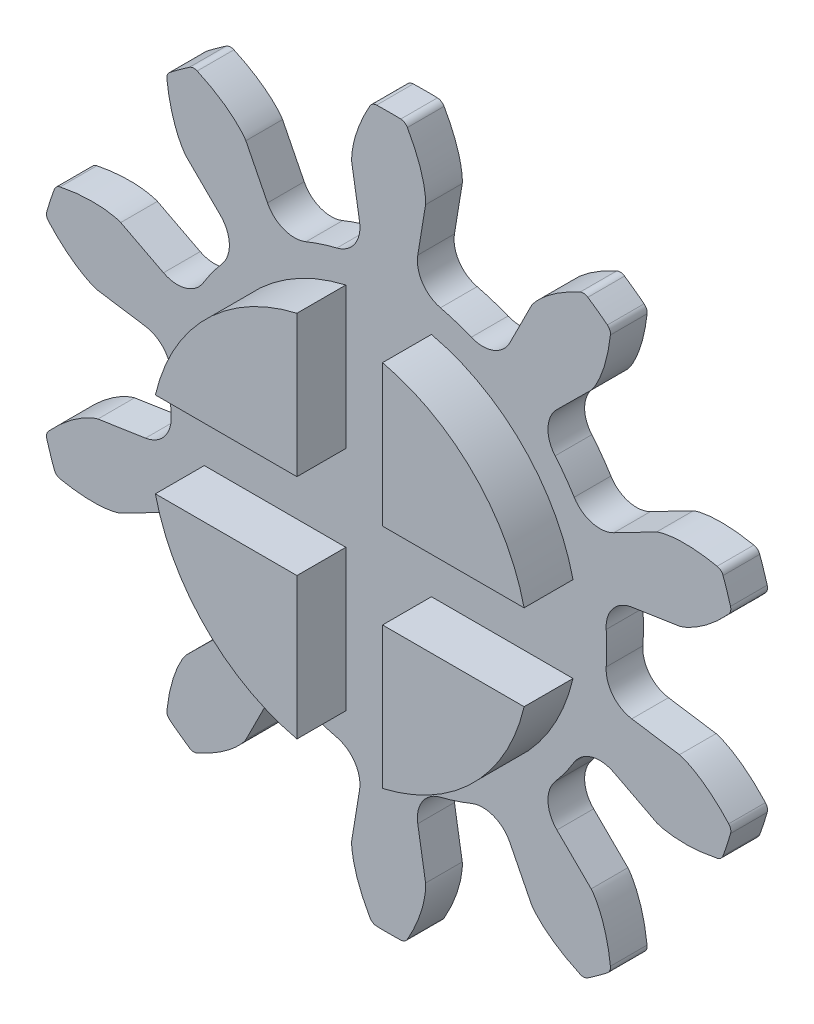
SolidWorks part; units mm, degrees
ref_plane "Front Plane" through (0, 0, 0) normal (0, 0, 1) x (1, 0, 0)
ref_plane "Top Plane" through (0, 0, 0) normal (0, 1, 0) x (1, 0, 0)
ref_plane "Right Plane" through (0, 0, 0) normal (1, 0, 0) x (0, 0, -1)
sketch "Sketch1" plane through (0, 0, 0) normal (0, 0, 1) x (1, 0, 0)
  circle A0 centre (0, 0) radius 38.1
  dimension "D1" = 76.2
extrude "Boss-Extrude1" add sketch "Sketch1" along normal blind 3.81
sketch "Sketch2" plane through (0, 0, 0) normal (0, 0, 1) x (1, 0, 0)
  line L0 (30.3864, 4.6402) -> (0, 0) construction
  line L1 (0, 0) -> (30.3864, -4.6402) construction
  line L2 (30.3864, -4.6402) -> (23.5396, -3.5946)
  line L3 (30.3864, 4.6402) -> (23.5396, 3.5946)
  line L4 (0, 0) -> (31.3591, -4.9668) construction
  circle A0 centre (0, 0) radius 38.1 construction
  circle A1 centre (0, 0) radius 23.8125 construction
  circle A2 centre (0, 0) radius 30.7387 construction
  circle A3 centre (0, 0) radius 31.75 construction
  arc A4 (36.8988, 9.4914) -> (36.8988, -9.4914) centre (48.4711, 0) cw
  arc A5 (23.5396, 3.5946) -> (23.5396, -3.5946) centre (0, 0) cw
  spline S0 degree 4 poles (30.3864, 4.6402) (30.3985, 4.6422) (30.4321, 4.6485) (30.4952, 4.6626) (30.5976, 4.6888) (30.7269, 4.7269) (30.8928, 4.7816) (31.0863, 4.8528) (31.2968, 4.9382) (31.5235, 5.0388) (31.7473, 5.1459) (31.9683, 5.2589) (32.1864, 5.377) (32.448, 5.5266) (32.7579, 5.715) (33.1145, 5.9482) (33.5119, 6.2279) (33.9091, 6.5289) (34.2933, 6.8381) (34.6734, 7.1653) (35.0354, 7.4922) (35.4028, 7.8465) (35.7374, 8.181) (36.1023, 8.5717) (36.3938, 8.8916) (36.7672, 9.3302) (36.9844, 9.5942) (37.2346, 9.9087) (37.3436, 10.0513) (37.4108, 10.139) knots 0 0 0 0 0 0.005377 0.015084 0.028532 0.04661 0.064855 0.092111 0.119476 0.146842 0.174209 0.201575 0.228941 0.256307 0.307035 0.361767 0.4165 0.471232 0.525964 0.580697 0.635429 0.690161 0.744894 0.799626 0.854358 0.909091 0.954545 1 1 1 1 1 construction
  spline S1 degree 4 poles (30.3864, 4.6402) (30.3985, 4.6422) (30.4321, 4.6485) (30.4952, 4.6626) (30.5976, 4.6888) (30.7269, 4.7269) (30.8928, 4.7816) (31.0863, 4.8528) (31.2968, 4.9382) (31.5235, 5.0388) (31.7473, 5.1459) (31.9683, 5.2589) (32.1864, 5.377) (32.448, 5.5266) (32.7579, 5.715) (33.1145, 5.9482) (33.5119, 6.2279) (33.9091, 6.5289) (34.2933, 6.8381) (34.6734, 7.1653) (35.0354, 7.4922) (35.4028, 7.8465) (35.7374, 8.181) (36.1023, 8.5717) (36.3938, 8.8916) (36.6863, 9.2351) (36.8273, 9.4042) (36.8988, 9.4914) knots 0 0 0 0 0 0.005377 0.015084 0.028532 0.04661 0.064855 0.092111 0.119476 0.146842 0.174209 0.201575 0.228941 0.256307 0.307035 0.361767 0.4165 0.471232 0.525964 0.580697 0.635429 0.690161 0.744894 0.799626 0.854358 0.909091 0.909091 0.909091 0.909091 0.909091
  spline S2 degree 4 poles (30.3864, -4.6402) (30.3985, -4.6422) (30.4321, -4.6485) (30.4952, -4.6626) (30.5976, -4.6888) (30.7269, -4.7269) (30.8928, -4.7816) (31.0863, -4.8528) (31.2968, -4.9382) (31.5235, -5.0388) (31.7473, -5.1459) (31.9683, -5.2589) (32.1864, -5.377) (32.448, -5.5266) (32.7579, -5.715) (33.1145, -5.9482) (33.5119, -6.2279) (33.9091, -6.5289) (34.2933, -6.8381) (34.6734, -7.1653) (35.0354, -7.4922) (35.4028, -7.8465) (35.7374, -8.181) (36.1023, -8.5717) (36.3938, -8.8916) (36.7672, -9.3302) (36.9844, -9.5942) (37.2346, -9.9087) (37.3436, -10.0513) (37.4108, -10.139) knots 0 0 0 0 0 0.005377 0.015084 0.028532 0.04661 0.064855 0.092111 0.119476 0.146842 0.174209 0.201575 0.228941 0.256307 0.307035 0.361767 0.4165 0.471232 0.525964 0.580697 0.635429 0.690161 0.744894 0.799626 0.854358 0.909091 0.954545 1 1 1 1 1 construction
  spline S3 degree 4 poles (30.3864, -4.6402) (30.3985, -4.6422) (30.4321, -4.6485) (30.4952, -4.6626) (30.5976, -4.6888) (30.7269, -4.7269) (30.8928, -4.7816) (31.0863, -4.8528) (31.2968, -4.9382) (31.5235, -5.0388) (31.7473, -5.1459) (31.9683, -5.2589) (32.1864, -5.377) (32.448, -5.5266) (32.7579, -5.715) (33.1145, -5.9482) (33.5119, -6.2279) (33.9091, -6.5289) (34.2933, -6.8381) (34.6734, -7.1653) (35.0354, -7.4922) (35.4028, -7.8465) (35.7374, -8.181) (36.1023, -8.5717) (36.3938, -8.8916) (36.6863, -9.2351) (36.8273, -9.4042) (36.8988, -9.4914) knots 0 0 0 0 0 0.005377 0.015084 0.028532 0.04661 0.064855 0.092111 0.119476 0.146842 0.174209 0.201575 0.228941 0.256307 0.307035 0.361767 0.4165 0.471232 0.525964 0.580697 0.635429 0.690161 0.744894 0.799626 0.854358 0.909091 0.909091 0.909091 0.909091 0.909091
  dimension "D1" = 76.2
  dimension "D2" = 63.5
  dimension "D3" = 61.4774
  dimension "D4" = 47.625
extrude "Cut-Extrude1" cut sketch "Sketch2" along normal blind 12.7
fillet "Fillet1" radius 1.985 4 edges at (36.8988, -9.4914, 1.905) (23.5396, -3.5946, 1.905) (23.5396, 3.5946, 1.905) (36.8988, 9.4914, 1.905)
pattern_circular "CirPattern1" count 10 over 360 about axis through (0, 0, 3.81) along (0, 0, -1) of "Fillet1", "Cut-Extrude1"
sketch "Sketch7" plane through (0, 0, 0) normal (0, 0, -1) x (-1, 0, 0)
  line L1 (-4.9989, -33.0345) -> (4.9989, -33.0345)
  line L2 (-4.9989, -33.0345) -> (-4.9989, 33.0345)
  line L3 (-4.9989, 33.0345) -> (4.9989, 33.0345)
  line L4 (4.9989, -33.0345) -> (4.9989, 33.0345)
  line L5 (-4.9989, -33.0345) -> (4.9989, 33.0345) construction
  line L6 (-4.9989, 33.0345) -> (4.9989, -33.0345) construction
  spline S0 degree 4 poles (4.9769, 30.3331) (4.9786, 30.3452) (4.9831, 30.3791) (4.9892, 30.4435) (4.9959, 30.5489) (4.9996, 30.6837) (4.9988, 30.8584) (4.9909, 31.0644) (4.9747, 31.2911) (4.9491, 31.5377) (4.9164, 31.7836) (4.8773, 32.0288) (4.8323, 32.2727) (4.7709, 32.5677) (4.6874, 32.9207) (4.5758, 33.3319) (4.4327, 33.7963) (4.2691, 34.267) (4.0937, 34.7279) (3.9001, 35.1905) (3.701, 35.6359) (3.4776, 36.0947) (3.2758, 36.491) (3.0998, 36.811) (2.9963, 36.9957) (2.9516, 37.0743) knots 0 0 0 0 0 0.005377 0.015084 0.028532 0.04661 0.064855 0.092111 0.119476 0.146842 0.174209 0.201575 0.228941 0.256307 0.307035 0.361767 0.4165 0.471232 0.525964 0.580697 0.635429 0.690161 0.744894 0.786423 0.786423 0.786423 0.786423 0.786423 construction
  point P0 (0, 0)
sketch "Sketch5" plane through (0, 0, 0) normal (0, 0, 1) x (1, 0, 0)
  line L60 (25.2517, 5.0258) -> (30.196, 5.7808)
  line L62 (25.2517, 5.0258) -> (30.196, 5.7808)
  line L64 (30.196, -5.7808) -> (25.2517, -5.0258)
  line L66 (30.196, -5.7808) -> (25.2517, -5.0258)
  line L68 (23.3831, -10.7766) -> (27.8269, -13.072)
  line L70 (23.3831, -10.7766) -> (27.8269, -13.072)
  line L72 (21.0312, -22.4255) -> (17.475, -18.9085)
  line L74 (21.0312, -22.4255) -> (17.475, -18.9085)
  line L128 (12.583, -22.4627) -> (14.8289, -26.9317)
  line L130 (12.583, -22.4627) -> (14.8289, -26.9317)
  line L132 (3.8332, -30.5045) -> (3.0234, -25.5688)
  line L136 (3.8332, -30.5045) -> (3.0234, -25.5688)
  line L140 (-3.0234, -25.5688) -> (-3.8332, -30.5045)
  line L144 (-3.0234, -25.5688) -> (-3.8332, -30.5045)
  line L148 (-14.8289, -26.9317) -> (-12.583, -22.4627)
  line L152 (-14.8289, -26.9317) -> (-12.583, -22.4627)
  line L156 (-17.475, -18.9085) -> (-21.0312, -22.4255)
  line L160 (-17.475, -18.9085) -> (-21.0312, -22.4255)
  line L161 (-27.8269, -13.072) -> (-23.3831, -10.7766)
  line L162 (-27.8269, -13.072) -> (-23.3831, -10.7766)
  line L163 (-25.2517, -5.0258) -> (-30.196, -5.7808)
  line L164 (-25.2517, -5.0258) -> (-30.196, -5.7808)
  line L165 (-30.196, 5.7808) -> (-25.2517, 5.0258)
  line L166 (-30.196, 5.7808) -> (-25.2517, 5.0258)
  line L167 (-23.3831, 10.7766) -> (-27.8269, 13.072)
  line L168 (-23.3831, 10.7766) -> (-27.8269, 13.072)
  line L169 (-21.0312, 22.4255) -> (-17.475, 18.9085)
  line L170 (-21.0312, 22.4255) -> (-17.475, 18.9085)
  line L171 (-12.583, 22.4627) -> (-14.8289, 26.9317)
  line L172 (-12.583, 22.4627) -> (-14.8289, 26.9317)
  line L173 (-3.8332, 30.5045) -> (-3.0234, 25.5688)
  line L174 (-3.8332, 30.5045) -> (-3.0234, 25.5688)
  line L175 (3.0234, 25.5688) -> (3.8332, 30.5045)
  line L176 (3.0234, 25.5688) -> (3.8332, 30.5045)
  line L177 (14.8289, 26.9317) -> (12.583, 22.4627)
  line L178 (14.8289, 26.9317) -> (12.583, 22.4627)
  line L179 (17.475, 18.9085) -> (21.0312, 22.4255)
  line L180 (17.475, 18.9085) -> (21.0312, 22.4255)
  line L184 (27.8269, 13.072) -> (23.3831, 10.7766)
  line L188 (27.8269, 13.072) -> (23.3831, 10.7766)
  arc A206 (25.2517, 5.0258) -> (22.5933, 1.6866) centre (25.7259, 1.9205) ccw
  arc A207 (25.2517, 5.0258) -> (22.5933, 1.6866) centre (25.7259, 1.9205) ccw
  arc A208 (22.5933, -1.6866) -> (22.5933, 1.6866) centre (0, 0) ccw
  arc A209 (22.5933, -1.6866) -> (22.5933, 1.6866) centre (0, 0) ccw
  arc A210 (22.5933, -1.6866) -> (25.2517, -5.0258) centre (25.7259, -1.9205) ccw
  arc A211 (22.5933, -1.6866) -> (25.2517, -5.0258) centre (25.7259, -1.9205) ccw
  arc A215 (35.5027, -10.2174) -> (35.3182, -9.4293) centre (34.7063, -9.9882) ccw
  arc A221 (35.5027, -10.2174) -> (35.3182, -9.4293) centre (34.7063, -9.9882) ccw
  arc A223 (34.7279, -12.6019) -> (35.5027, -10.2174) centre (0, 0) ccw
  arc A227 (34.7279, -12.6019) -> (35.5027, -10.2174) centre (0, 0) ccw
  arc A233 (34.1154, -13.131) -> (34.7279, -12.6019) centre (33.9489, -12.3192) ccw
  arc A239 (34.1154, -13.131) -> (34.7279, -12.6019) centre (33.9489, -12.3192) ccw
  arc A245 (23.3831, -10.7766) -> (19.2698, -11.9155) centre (21.9415, -13.5676) ccw
  arc A251 (23.3831, -10.7766) -> (19.2698, -11.9155) centre (21.9415, -13.5676) ccw
  arc A257 (17.287, -14.6445) -> (19.2698, -11.9155) centre (0, 0) ccw
  arc A263 (17.287, -14.6445) -> (19.2698, -11.9155) centre (0, 0) ccw
  arc A269 (17.287, -14.6445) -> (17.475, -18.9085) centre (19.6838, -16.675) ccw
  arc A275 (17.287, -14.6445) -> (17.475, -18.9085) centre (19.6838, -16.675) ccw
  arc A281 (12.583, -22.4627) -> (8.5858, -20.9663) centre (9.7762, -23.8733) ccw
  arc A287 (12.583, -22.4627) -> (8.5858, -20.9663) centre (9.7762, -23.8733) ccw
  arc A388 (5.3776, -22.0087) -> (8.5858, -20.9663) centre (0, 0) ccw
  arc A390 (5.3776, -22.0087) -> (8.5858, -20.9663) centre (0, 0) ccw
  arc A394 (5.3776, -22.0087) -> (3.0234, -25.5688) centre (6.1232, -25.0602) ccw
  arc A400 (5.3776, -22.0087) -> (3.0234, -25.5688) centre (6.1232, -25.0602) ccw
  arc A402 (1.2536, -36.9224) -> (1.9461, -36.5034) centre (1.2255, -36.0942) ccw
  arc A406 (1.2536, -36.9224) -> (1.9461, -36.5034) centre (1.2255, -36.0942) ccw
  arc A412 (-1.2536, -36.9224) -> (1.2536, -36.9224) centre (0, 0) ccw
  arc A414 (-1.2536, -36.9224) -> (1.2536, -36.9224) centre (0, 0) ccw
  arc A418 (-1.9461, -36.5034) -> (-1.2536, -36.9224) centre (-1.2255, -36.0942) ccw
  arc A424 (-1.9461, -36.5034) -> (-1.2536, -36.9224) centre (-1.2255, -36.0942) ccw
  arc A426 (-3.0234, -25.5688) -> (-5.3776, -22.0087) centre (-6.1232, -25.0602) ccw
  arc A430 (-3.0234, -25.5688) -> (-5.3776, -22.0087) centre (-6.1232, -25.0602) ccw
  arc A436 (-8.5858, -20.9663) -> (-5.3776, -22.0087) centre (0, 0) ccw
  arc A438 (-8.5858, -20.9663) -> (-5.3776, -22.0087) centre (0, 0) ccw
  arc A442 (-8.5858, -20.9663) -> (-12.583, -22.4627) centre (-9.7762, -23.8733) ccw
  arc A448 (-8.5858, -20.9663) -> (-12.583, -22.4627) centre (-9.7762, -23.8733) ccw
  arc A450 (-17.475, -18.9085) -> (-17.287, -14.6445) centre (-19.6838, -16.675) ccw
  arc A454 (-17.475, -18.9085) -> (-17.287, -14.6445) centre (-19.6838, -16.675) ccw
  arc A460 (-19.2698, -11.9155) -> (-17.287, -14.6445) centre (0, 0) ccw
  arc A462 (-19.2698, -11.9155) -> (-17.287, -14.6445) centre (0, 0) ccw
  arc A466 (-19.2698, -11.9155) -> (-23.3831, -10.7766) centre (-21.9415, -13.5676) ccw
  arc A472 (-19.2698, -11.9155) -> (-23.3831, -10.7766) centre (-21.9415, -13.5676) ccw
  arc A474 (-34.7279, -12.6019) -> (-34.1154, -13.131) centre (-33.9489, -12.3192) ccw
  arc A478 (-34.7279, -12.6019) -> (-34.1154, -13.131) centre (-33.9489, -12.3192) ccw
  arc A481 (35.5027, 10.2174) -> (34.7279, 12.6019) centre (0, 0) ccw
  arc A482 (35.3182, 9.4293) -> (35.5027, 10.2174) centre (34.7063, 9.9882) ccw
  arc A483 (-35.5027, -10.2174) -> (-34.7279, -12.6019) centre (0, 0) ccw
  arc A492 (22.7166, -29.134) -> (23.0306, -28.388) centre (22.2071, -28.4805) ccw
  arc A493 (20.6883, -30.6077) -> (22.7166, -29.134) centre (0, 0) ccw
  arc A494 (19.8817, -30.6758) -> (20.6883, -30.6077) centre (20.2242, -29.9212) ccw
  arc A502 (-35.5027, -10.2174) -> (-34.7279, -12.6019) centre (0, 0) ccw
  arc A503 (-35.3182, -9.4293) -> (-35.5027, -10.2174) centre (-34.7063, -9.9882) ccw
  arc A504 (-20.6883, -30.6077) -> (-19.8817, -30.6758) centre (-20.2242, -29.9212) ccw
  arc A505 (-22.7166, -29.134) -> (-20.6883, -30.6077) centre (0, 0) ccw
  arc A506 (-23.0306, -28.388) -> (-22.7166, -29.134) centre (-22.2071, -28.4805) ccw
  arc A507 (-35.3182, -9.4293) -> (-35.5027, -10.2174) centre (-34.7063, -9.9882) ccw
  arc A508 (-25.2517, -5.0258) -> (-22.5933, -1.6866) centre (-25.7259, -1.9205) ccw
  arc A509 (-25.2517, -5.0258) -> (-22.5933, -1.6866) centre (-25.7259, -1.9205) ccw
  arc A510 (-22.5933, 1.6866) -> (-22.5933, -1.6866) centre (0, 0) ccw
  arc A511 (-22.5933, 1.6866) -> (-22.5933, -1.6866) centre (0, 0) ccw
  arc A512 (-22.5933, 1.6866) -> (-25.2517, 5.0258) centre (-25.7259, 1.9205) ccw
  arc A513 (-22.5933, 1.6866) -> (-25.2517, 5.0258) centre (-25.7259, 1.9205) ccw
  arc A514 (-23.3831, 10.7766) -> (-19.2698, 11.9155) centre (-21.9415, 13.5676) ccw
  arc A515 (-23.3831, 10.7766) -> (-19.2698, 11.9155) centre (-21.9415, 13.5676) ccw
  arc A516 (-35.5027, 10.2174) -> (-35.3182, 9.4293) centre (-34.7063, 9.9882) ccw
  arc A517 (-34.7279, 12.6019) -> (-35.5027, 10.2174) centre (0, 0) ccw
  arc A518 (-34.1154, 13.131) -> (-34.7279, 12.6019) centre (-33.9489, 12.3192) ccw
  arc A519 (-17.287, 14.6445) -> (-19.2698, 11.9155) centre (0, 0) ccw
  arc A520 (-17.287, 14.6445) -> (-19.2698, 11.9155) centre (0, 0) ccw
  arc A521 (-17.287, 14.6445) -> (-17.475, 18.9085) centre (-19.6838, 16.675) ccw
  arc A522 (-17.287, 14.6445) -> (-17.475, 18.9085) centre (-19.6838, 16.675) ccw
  arc A523 (-22.7166, 29.134) -> (-23.0306, 28.388) centre (-22.2071, 28.4805) ccw
  arc A524 (-22.7166, 29.134) -> (-23.0306, 28.388) centre (-22.2071, 28.4805) ccw
  arc A525 (-20.6883, 30.6077) -> (-22.7166, 29.134) centre (0, 0) ccw
  arc A526 (-20.6883, 30.6077) -> (-22.7166, 29.134) centre (0, 0) ccw
  arc A527 (-19.8817, 30.6758) -> (-20.6883, 30.6077) centre (-20.2242, 29.9212) ccw
  arc A528 (-1.2536, 36.9224) -> (-1.9461, 36.5034) centre (-1.2255, 36.0942) ccw
  arc A529 (1.2536, 36.9224) -> (-1.2536, 36.9224) centre (0, 0) ccw
  arc A530 (1.9461, 36.5034) -> (1.2536, 36.9224) centre (1.2255, 36.0942) ccw
  arc A531 (-19.8817, 30.6758) -> (-20.6883, 30.6077) centre (-20.2242, 29.9212) ccw
  arc A532 (-12.583, 22.4627) -> (-8.5858, 20.9663) centre (-9.7762, 23.8733) ccw
  arc A533 (-12.583, 22.4627) -> (-8.5858, 20.9663) centre (-9.7762, 23.8733) ccw
  arc A534 (-5.3776, 22.0087) -> (-8.5858, 20.9663) centre (0, 0) ccw
  arc A535 (-5.3776, 22.0087) -> (-8.5858, 20.9663) centre (0, 0) ccw
  arc A536 (-5.3776, 22.0087) -> (-3.0234, 25.5688) centre (-6.1232, 25.0602) ccw
  arc A537 (-5.3776, 22.0087) -> (-3.0234, 25.5688) centre (-6.1232, 25.0602) ccw
  arc A538 (3.0234, 25.5688) -> (5.3776, 22.0087) centre (6.1232, 25.0602) ccw
  arc A539 (3.0234, 25.5688) -> (5.3776, 22.0087) centre (6.1232, 25.0602) ccw
  arc A540 (34.7279, 12.6019) -> (34.1154, 13.131) centre (33.9489, 12.3192) ccw
  arc A544 (8.5858, 20.9663) -> (5.3776, 22.0087) centre (0, 0) ccw
  arc A546 (8.5858, 20.9663) -> (5.3776, 22.0087) centre (0, 0) ccw
  arc A548 (8.5858, 20.9663) -> (12.583, 22.4627) centre (9.7762, 23.8733) ccw
  arc A550 (8.5858, 20.9663) -> (12.583, 22.4627) centre (9.7762, 23.8733) ccw
  arc A552 (20.6883, 30.6077) -> (19.8817, 30.6758) centre (20.2242, 29.9212) ccw
  arc A554 (20.6883, 30.6077) -> (19.8817, 30.6758) centre (20.2242, 29.9212) ccw
  arc A556 (22.7166, 29.134) -> (20.6883, 30.6077) centre (0, 0) ccw
  arc A558 (22.7166, 29.134) -> (20.6883, 30.6077) centre (0, 0) ccw
  arc A560 (23.0306, 28.388) -> (22.7166, 29.134) centre (22.2071, 28.4805) ccw
  arc A562 (23.0306, 28.388) -> (22.7166, 29.134) centre (22.2071, 28.4805) ccw
  arc A564 (17.475, 18.9085) -> (17.287, 14.6445) centre (19.6838, 16.675) ccw
  arc A568 (17.475, 18.9085) -> (17.287, 14.6445) centre (19.6838, 16.675) ccw
  arc A572 (19.2698, 11.9155) -> (17.287, 14.6445) centre (0, 0) ccw
  arc A577 (35.5027, 10.2174) -> (34.7279, 12.6019) centre (0, 0) ccw
  arc A578 (35.3182, 9.4293) -> (35.5027, 10.2174) centre (34.7063, 9.9882) ccw
  arc A588 (22.7166, -29.134) -> (23.0306, -28.388) centre (22.2071, -28.4805) ccw
  arc A589 (20.6883, -30.6077) -> (22.7166, -29.134) centre (0, 0) ccw
  arc A590 (19.8817, -30.6758) -> (20.6883, -30.6077) centre (20.2242, -29.9212) ccw
  arc A600 (-20.6883, -30.6077) -> (-19.8817, -30.6758) centre (-20.2242, -29.9212) ccw
  arc A601 (-22.7166, -29.134) -> (-20.6883, -30.6077) centre (0, 0) ccw
  arc A602 (-23.0306, -28.388) -> (-22.7166, -29.134) centre (-22.2071, -28.4805) ccw
  arc A612 (-35.5027, 10.2174) -> (-35.3182, 9.4293) centre (-34.7063, 9.9882) ccw
  arc A613 (-34.7279, 12.6019) -> (-35.5027, 10.2174) centre (0, 0) ccw
  arc A614 (-34.1154, 13.131) -> (-34.7279, 12.6019) centre (-33.9489, 12.3192) ccw
  arc A624 (-1.2536, 36.9224) -> (-1.9461, 36.5034) centre (-1.2255, 36.0942) ccw
  arc A625 (1.2536, 36.9224) -> (-1.2536, 36.9224) centre (0, 0) ccw
  arc A626 (1.9461, 36.5034) -> (1.2536, 36.9224) centre (1.2255, 36.0942) ccw
  arc A636 (34.7279, 12.6019) -> (34.1154, 13.131) centre (33.9489, 12.3192) ccw
  arc A672 (19.2698, 11.9155) -> (17.287, 14.6445) centre (0, 0) ccw
  arc A674 (19.2698, 11.9155) -> (23.3831, 10.7766) centre (21.9415, 13.5676) ccw
  arc A676 (19.2698, 11.9155) -> (23.3831, 10.7766) centre (21.9415, 13.5676) ccw
  spline S40 degree 3 poles (1976.0685, 2276.1578) (-51.5515, -245.3086) (71.3348, -36.1291) (32.5584, -6.9602) (32.1168, -6.6652) (31.4219, -6.2752) (31.186, -6.1548) (30.8237, -5.994) (30.7014, -5.9438) (30.515, -5.8754) (30.4524, -5.8538) (25.1699, -4.1907) (18.0958, -6.8225) (-1178.4876, -2750.7659) knots -22.08418 -22.08418 -22.08418 -22.08418 0.5 0.5 0.75 0.75 0.875 0.875 0.9375 0.9375 0.96875 0.96875 3.542779 3.542779 3.542779 3.542779 only from (35.3182, -9.4293) to (30.196, -5.7808)
  spline S41 degree 3 poles (35.3182, -9.4293) (34.6021, -8.6454) (33.832, -7.9183) (32.5584, -6.9602) (32.1168, -6.6652) (31.4219, -6.2752) (31.186, -6.1548) (30.8237, -5.994) (30.7014, -5.9438) (30.515, -5.8754) (30.4524, -5.8538) (30.3257, -5.8139) (30.262, -5.7946) (30.196, -5.7808) knots 0 0 0 0 0.5 0.5 0.75 0.75 0.875 0.875 0.9375 0.9375 0.96875 0.96875 1 1 1 1
  spline S42 degree 3 poles (1266.5255, 2718.8832) (18.2349, -4.3484) (22.7434, -11.3749) (28.0764, -13.1634) (28.14, -13.1828) (28.3315, -13.2372) (28.4603, -13.2685) (28.8493, -13.3517) (29.112, -13.393) (29.9009, -13.4854) (30.432, -13.5063) (77.75, -12.7232) (116.0288, 218.9821) (-861.909, -2876.0301) knots -2.583253 -2.583253 -2.583253 -2.583253 0.03125 0.03125 0.0625 0.0625 0.125 0.125 0.25 0.25 0.5 0.5 22.580594 22.580594 22.580594 22.580594 only from (27.8269, -13.072) to (34.1154, -13.131)
  spline S43 degree 3 poles (27.8269, -13.072) (27.8876, -13.0993) (27.9505, -13.1211) (28.0764, -13.1634) (28.14, -13.1828) (28.3315, -13.2372) (28.4603, -13.2685) (28.8493, -13.3517) (29.112, -13.393) (29.9009, -13.4854) (30.432, -13.5063) (32.0212, -13.48) (33.0763, -13.3441) (34.1154, -13.131) knots 0 0 0 0 0.03125 0.03125 0.0625 0.0625 0.125 0.125 0.25 0.25 0.5 0.5 1 1 1 1
  spline S44 degree 3 poles (2775.3934, -1175.9814) (-249.2327, -26.7761) (-12.3172, -79.0079) (3.4415, -33.1157) (3.5856, -32.6046) (3.7419, -31.8231) (3.7835, -31.5616) (3.8244, -31.1673) (3.8344, -31.0355) (3.8418, -30.8371) (3.843, -30.7709) (3.7923, -25.233) (-0.8966, -19.3184) (-2980.3065, 270.7749) knots -22.08418 -22.08418 -22.08418 -22.08418 0.5 0.5 0.75 0.75 0.875 0.875 0.9375 0.9375 0.96875 0.96875 3.542779 3.542779 3.542779 3.542779 only from (1.9461, -36.5034) to (3.8332, -30.5045)
  spline S45 degree 3 poles (1.9461, -36.5034) (2.4704, -35.5801) (2.9239, -34.623) (3.4415, -33.1157) (3.5856, -32.6046) (3.7419, -31.8231) (3.7835, -31.5616) (3.8244, -31.1673) (3.8344, -31.0355) (3.8418, -30.8371) (3.843, -30.7709) (3.8418, -30.638) (3.8405, -30.5715) (3.8332, -30.5045) knots 0 0 0 0 0.5 0.5 0.75 0.75 0.875 0.875 0.9375 0.9375 0.96875 0.96875 1 1 1 1
  spline S46 degree 3 poles (2977.1894, -364.3562) (1.4993, -18.6862) (-3.7901, -25.1453) (-3.843, -30.77) (-3.8419, -30.8365) (-3.8344, -31.0354) (-3.8244, -31.1676) (-3.7833, -31.5632) (-3.7414, -31.8258) (-3.5855, -32.6047) (-3.4413, -33.1162) (11.9256, -77.8763) (244.1192, -42.6807) (-3001.6117, -69.018) knots -2.583253 -2.583253 -2.583253 -2.583253 0.03125 0.03125 0.0625 0.0625 0.125 0.125 0.25 0.25 0.5 0.5 22.580594 22.580594 22.580594 22.580594 only from (-3.8332, -30.5045) to (-1.9461, -36.5034)
  spline S47 degree 3 poles (-3.8332, -30.5045) (-3.8404, -30.5706) (-3.8418, -30.6371) (-3.843, -30.77) (-3.8419, -30.8365) (-3.8344, -31.0354) (-3.8244, -31.1676) (-3.7833, -31.5632) (-3.7414, -31.8258) (-3.5855, -32.6047) (-3.4413, -33.1162) (-2.9252, -34.6195) (-2.4698, -35.581) (-1.9461, -36.5034) knots 0 0 0 0 0.03125 0.03125 0.0625 0.0625 0.125 0.125 0.25 0.25 0.5 0.5 1 1 1 1
  spline S48 degree 3 poles (-260.781, -3002.9542) (-102.4827, 228.7601) (-78.9472, -12.7005) (-30.4314, -13.5064) (-29.9008, -13.4855) (-29.1093, -13.3926) (-28.8477, -13.3514) (-28.4601, -13.2685) (-28.3316, -13.2373) (-28.1407, -13.183) (-28.0773, -13.1636) (-22.8261, -11.4041) (-18.65, -5.117) (-663.4432, 2918.114) knots -22.08418 -22.08418 -22.08418 -22.08418 0.5 0.5 0.75 0.75 0.875 0.875 0.9375 0.9375 0.96875 0.96875 3.542779 3.542779 3.542779 3.542779 only from (-34.1154, -13.131) to (-27.8269, -13.072)
  spline S49 degree 3 poles (-34.1154, -13.131) (-33.0753, -13.3443) (-32.0249, -13.4799) (-30.4314, -13.5064) (-29.9008, -13.4855) (-29.1093, -13.3926) (-28.8477, -13.3514) (-28.4601, -13.2685) (-28.3316, -13.2373) (-28.1407, -13.183) (-28.0773, -13.1636) (-27.9513, -13.1214) (-27.8885, -13.0997) (-27.8269, -13.072) knots 0 0 0 0 0.5 0.5 0.75 0.75 0.875 0.875 0.9375 0.9375 0.96875 0.96875 1 1 1 1
  spline S50 degree 3 poles (573.4788, -2944.0677) (-17.3083, -7.2002) (-25.0858, -4.1657) (-30.4516, -5.8535) (-30.5144, -5.8752) (-30.7013, -5.9437) (-30.8239, -5.9941) (-31.1875, -6.1554) (-31.4243, -6.2765) (-32.1169, -6.6654) (-32.5588, -6.9606) (-70.3795, -35.407) (34.8452, -245.3603) (-993.189, 2833.3746) knots -2.583253 -2.583253 -2.583253 -2.583253 0.03125 0.03125 0.0625 0.0625 0.125 0.125 0.25 0.25 0.5 0.5 22.580594 22.580594 22.580594 22.580594 only from (-30.196, -5.7808) to (-35.3182, -9.4293)
  spline S51 degree 3 poles (-30.196, -5.7808) (-30.2611, -5.7944) (-30.3248, -5.8137) (-30.4516, -5.8535) (-30.5144, -5.8752) (-30.7013, -5.9437) (-30.8239, -5.9941) (-31.1875, -6.1554) (-31.4243, -6.2765) (-32.1169, -6.6654) (-32.5588, -6.9606) (-33.8291, -7.916) (-34.6028, -8.6462) (-35.3182, -9.4293) knots 0 0 0 0 0.03125 0.03125 0.0625 0.0625 0.125 0.125 0.25 0.25 0.5 0.5 1 1 1 1
  spline S52 degree 3 poles (-2936.5649, -679.9464) (185.8948, 168.1576) (-36.4749, 71.1586) (-22.2491, 24.7683) (-22.0653, 24.2701) (-21.7324, 23.546) (-21.6124, 23.31) (-21.4137, 22.967) (-21.3443, 22.8545) (-21.2337, 22.6896) (-21.1957, 22.6353) (-17.8996, 18.1849) (-10.6297, 16.156) (2570.2761, 1532.7187) knots -22.08418 -22.08418 -22.08418 -22.08418 0.5 0.5 0.75 0.75 0.875 0.875 0.9375 0.9375 0.96875 0.96875 3.542779 3.542779 3.542779 3.542779 only from (-23.0306, 28.388) to (-21.0312, 22.4255)
  spline S53 degree 3 poles (-23.0306, 28.388) (-22.912, 27.3329) (-22.7164, 26.292) (-22.2491, 24.7683) (-22.0653, 24.2701) (-21.7324, 23.546) (-21.6124, 23.31) (-21.4137, 22.967) (-21.3443, 22.8545) (-21.2337, 22.6896) (-21.1957, 22.6353) (-21.1167, 22.5285) (-21.0765, 22.4755) (-21.0312, 22.4255) knots 0 0 0 0 0.5 0.5 0.75 0.75 0.875 0.875 0.9375 0.9375 0.96875 0.96875 1 1 1 1
  spline S54 degree 3 poles (-2622.76, -1455.1777) (-12.1964, 14.2362) (-11.7138, 22.5707) (-14.9771, 27.1523) (-15.0171, 27.2054) (-15.14, 27.362) (-15.2258, 27.463) (-15.4916, 27.759) (-15.6799, 27.9468) (-16.2638, 28.4853) (-16.6812, 28.8143) (-55.4225, 55.9935) (-222.5837, -108.9603) (2387.7871, 1820.1398) knots -2.583253 -2.583253 -2.583253 -2.583253 0.03125 0.03125 0.0625 0.0625 0.125 0.125 0.25 0.25 0.5 0.5 22.580594 22.580594 22.580594 22.580594 only from (-14.8289, 26.9317) to (-19.8817, 30.6758)
  spline S55 degree 3 poles (-14.8289, 26.9317) (-14.862, 26.9894) (-14.9, 27.0441) (-14.9771, 27.1523) (-15.0171, 27.2054) (-15.14, 27.362) (-15.2258, 27.463) (-15.4916, 27.759) (-15.6799, 27.9468) (-16.2638, 28.4853) (-16.6812, 28.8143) (-17.9823, 29.7272) (-18.9159, 30.2374) (-19.8817, 30.6758) knots 0 0 0 0 0.03125 0.03125 0.0625 0.0625 0.125 0.125 0.25 0.25 0.5 0.5 1 1 1 1
  spline S56 degree 3 poles (-1554.1159, 2582.7242) (217.3721, -124.8329) (56.4045, 56.6789) (16.6807, 28.814) (16.2637, 28.4853) (15.6779, 27.9448) (15.4905, 27.7578) (15.2257, 27.4628) (15.1401, 27.3621) (15.0175, 27.2059) (14.9776, 27.153) (11.7636, 22.643) (12.0805, 15.1019) (2251.9612, -1970.8417) knots -22.08418 -22.08418 -22.08418 -22.08418 0.5 0.5 0.75 0.75 0.875 0.875 0.9375 0.9375 0.96875 0.96875 3.542779 3.542779 3.542779 3.542779 only from (19.8817, 30.6758) to (14.8289, 26.9317)
  spline S57 degree 3 poles (19.8817, 30.6758) (18.9149, 30.2369) (17.9854, 29.7293) (16.6807, 28.814) (16.2637, 28.4853) (15.6779, 27.9448) (15.4905, 27.7578) (15.2257, 27.4628) (15.1401, 27.3621) (15.0175, 27.2059) (14.9776, 27.153) (14.9005, 27.0448) (14.8625, 26.9903) (14.8289, 26.9317) knots 0 0 0 0 0.5 0.5 0.75 0.75 0.875 0.875 0.9375 0.9375 0.96875 0.96875 1 1 1 1
  spline S58 degree 3 poles (-2194.4337, 2044.7184) (9.7705, 15.9987) (17.8463, 18.1152) (21.1952, 22.6346) (21.2333, 22.689) (21.3443, 22.8543) (21.4138, 22.9672) (21.6132, 23.3114) (21.7336, 23.5485) (22.0653, 24.2702) (22.2493, 24.7689) (36.1265, 70.0129) (-172.4095, 178.0191) (2468.9226, -1708.4664) knots -2.583253 -2.583253 -2.583253 -2.583253 0.03125 0.03125 0.0625 0.0625 0.125 0.125 0.25 0.25 0.5 0.5 22.580594 22.580594 22.580594 22.580594 only from (21.0312, 22.4255) to (23.0306, 28.388)
  spline S59 degree 3 poles (21.0312, 22.4255) (21.0759, 22.4748) (21.1161, 22.5278) (21.1952, 22.6346) (21.2333, 22.689) (21.3443, 22.8543) (21.4138, 22.9672) (21.6132, 23.3114) (21.7336, 23.5485) (22.0653, 24.2702) (22.2493, 24.7689) (22.7154, 26.2884) (22.9121, 27.3339) (23.0306, 28.388) knots 0 0 0 0 0.03125 0.03125 0.0625 0.0625 0.125 0.125 0.25 0.25 0.5 0.5 1 1 1 1
  spline S161 degree 3 poles (-573.4788, 2944.0677) (17.3083, 7.2002) (25.0858, 4.1657) (30.4516, 5.8535) (30.5144, 5.8752) (30.7013, 5.9437) (30.8239, 5.9941) (31.1875, 6.1554) (31.4243, 6.2765) (32.1169, 6.6654) (32.5588, 6.9606) (70.3795, 35.407) (-34.8452, 245.3603) (993.189, -2833.3746) knots -2.583253 -2.583253 -2.583253 -2.583253 0.03125 0.03125 0.0625 0.0625 0.125 0.125 0.25 0.25 0.5 0.5 22.580594 22.580594 22.580594 22.580594 only from (30.196, 5.7808) to (35.3182, 9.4293)
  spline S164 degree 3 poles (2936.5649, 679.9464) (-185.8948, -168.1576) (36.4749, -71.1586) (22.2491, -24.7683) (22.0653, -24.2701) (21.7324, -23.546) (21.6124, -23.31) (21.4137, -22.967) (21.3443, -22.8545) (21.2337, -22.6896) (21.1957, -22.6353) (17.8996, -18.1849) (10.6297, -16.156) (-2570.2761, -1532.7187) knots -22.08418 -22.08418 -22.08418 -22.08418 0.5 0.5 0.75 0.75 0.875 0.875 0.9375 0.9375 0.96875 0.96875 3.542779 3.542779 3.542779 3.542779 only from (23.0306, -28.388) to (21.0312, -22.4255)
  spline S165 degree 3 poles (2622.76, 1455.1777) (12.1964, -14.2362) (11.7138, -22.5707) (14.9771, -27.1523) (15.0171, -27.2054) (15.14, -27.362) (15.2258, -27.463) (15.4916, -27.759) (15.6799, -27.9468) (16.2638, -28.4853) (16.6812, -28.8143) (55.4225, -55.9935) (222.5837, 108.9603) (-2387.7871, -1820.1398) knots -2.583253 -2.583253 -2.583253 -2.583253 0.03125 0.03125 0.0625 0.0625 0.125 0.125 0.25 0.25 0.5 0.5 22.580594 22.580594 22.580594 22.580594 only from (14.8289, -26.9317) to (19.8817, -30.6758)
  spline S168 degree 3 poles (1554.1159, -2582.7242) (-217.3721, 124.8329) (-56.4045, -56.6789) (-16.6807, -28.814) (-16.2637, -28.4853) (-15.6779, -27.9448) (-15.4905, -27.7578) (-15.2257, -27.4628) (-15.1401, -27.3621) (-15.0175, -27.2059) (-14.9776, -27.153) (-11.7636, -22.643) (-12.0805, -15.1019) (-2251.9612, 1970.8417) knots -22.08418 -22.08418 -22.08418 -22.08418 0.5 0.5 0.75 0.75 0.875 0.875 0.9375 0.9375 0.96875 0.96875 3.542779 3.542779 3.542779 3.542779 only from (-19.8817, -30.6758) to (-14.8289, -26.9317)
  spline S169 degree 3 poles (2194.4337, -2044.7184) (-9.7705, -15.9987) (-17.8463, -18.1152) (-21.1952, -22.6346) (-21.2333, -22.689) (-21.3443, -22.8543) (-21.4138, -22.9672) (-21.6132, -23.3114) (-21.7336, -23.5485) (-22.0653, -24.2702) (-22.2493, -24.7689) (-36.1265, -70.0129) (172.4095, -178.0191) (-2468.9226, 1708.4664) knots -2.583253 -2.583253 -2.583253 -2.583253 0.03125 0.03125 0.0625 0.0625 0.125 0.125 0.25 0.25 0.5 0.5 22.580594 22.580594 22.580594 22.580594 only from (-21.0312, -22.4255) to (-23.0306, -28.388)
  spline S172 degree 3 poles (-1976.0685, -2276.1578) (51.5515, 245.3086) (-71.3348, 36.1291) (-32.5584, 6.9602) (-32.1168, 6.6652) (-31.4219, 6.2752) (-31.186, 6.1548) (-30.8237, 5.994) (-30.7014, 5.9438) (-30.515, 5.8754) (-30.4524, 5.8538) (-25.1699, 4.1907) (-18.0958, 6.8225) (1178.4876, 2750.7659) knots -22.08418 -22.08418 -22.08418 -22.08418 0.5 0.5 0.75 0.75 0.875 0.875 0.9375 0.9375 0.96875 0.96875 3.542779 3.542779 3.542779 3.542779 only from (-35.3182, 9.4293) to (-30.196, 5.7808)
  spline S173 degree 3 poles (-1266.5255, -2718.8832) (-18.2349, 4.3484) (-22.7434, 11.3749) (-28.0764, 13.1634) (-28.14, 13.1828) (-28.3315, 13.2372) (-28.4603, 13.2685) (-28.8493, 13.3517) (-29.112, 13.393) (-29.9009, 13.4854) (-30.432, 13.5063) (-77.75, 12.7232) (-116.0288, -218.9821) (861.909, 2876.0301) knots -2.583253 -2.583253 -2.583253 -2.583253 0.03125 0.03125 0.0625 0.0625 0.125 0.125 0.25 0.25 0.5 0.5 22.580594 22.580594 22.580594 22.580594 only from (-27.8269, 13.072) to (-34.1154, 13.131)
  spline S176 degree 3 poles (-2775.3934, 1175.9814) (249.2327, 26.7761) (12.3172, 79.0079) (-3.4415, 33.1157) (-3.5856, 32.6046) (-3.7419, 31.8231) (-3.7835, 31.5616) (-3.8244, 31.1673) (-3.8344, 31.0355) (-3.8418, 30.8371) (-3.843, 30.7709) (-3.7923, 25.233) (0.8966, 19.3184) (2980.3065, -270.7749) knots -22.08418 -22.08418 -22.08418 -22.08418 0.5 0.5 0.75 0.75 0.875 0.875 0.9375 0.9375 0.96875 0.96875 3.542779 3.542779 3.542779 3.542779 only from (-1.9461, 36.5034) to (-3.8332, 30.5045)
  spline S177 degree 3 poles (-2977.1894, 364.3562) (-1.4993, 18.6862) (3.7901, 25.1453) (3.843, 30.77) (3.8419, 30.8365) (3.8344, 31.0354) (3.8244, 31.1676) (3.7833, 31.5632) (3.7414, 31.8258) (3.5855, 32.6047) (3.4413, 33.1162) (-11.9256, 77.8763) (-244.1192, 42.6807) (3001.6117, 69.018) knots -2.583253 -2.583253 -2.583253 -2.583253 0.03125 0.03125 0.0625 0.0625 0.125 0.125 0.25 0.25 0.5 0.5 22.580594 22.580594 22.580594 22.580594 only from (3.8332, 30.5045) to (1.9461, 36.5034)
  spline S180 degree 3 poles (260.781, 3002.9542) (102.4827, -228.7601) (78.9472, 12.7005) (30.4314, 13.5064) (29.9008, 13.4855) (29.1093, 13.3926) (28.8477, 13.3514) (28.4601, 13.2685) (28.3316, 13.2373) (28.1407, 13.183) (28.0773, 13.1636) (22.8261, 11.4041) (18.65, 5.117) (663.4432, -2918.114) knots -22.08418 -22.08418 -22.08418 -22.08418 0.5 0.5 0.75 0.75 0.875 0.875 0.9375 0.9375 0.96875 0.96875 3.542779 3.542779 3.542779 3.542779 only from (34.1154, 13.131) to (27.8269, 13.072)
  spline S193 degree 3 poles (30.196, 5.7808) (30.2611, 5.7944) (30.3248, 5.8137) (30.4516, 5.8535) (30.5144, 5.8752) (30.7013, 5.9437) (30.8239, 5.9941) (31.1875, 6.1554) (31.4243, 6.2765) (32.1169, 6.6654) (32.5588, 6.9606) (33.8291, 7.916) (34.6028, 8.6462) (35.3182, 9.4293) knots 0 0 0 0 0.03125 0.03125 0.0625 0.0625 0.125 0.125 0.25 0.25 0.5 0.5 1 1 1 1
  spline S196 degree 3 poles (23.0306, -28.388) (22.912, -27.3329) (22.7164, -26.292) (22.2491, -24.7683) (22.0653, -24.2701) (21.7324, -23.546) (21.6124, -23.31) (21.4137, -22.967) (21.3443, -22.8545) (21.2337, -22.6896) (21.1957, -22.6353) (21.1167, -22.5285) (21.0765, -22.4755) (21.0312, -22.4255) knots 0 0 0 0 0.5 0.5 0.75 0.75 0.875 0.875 0.9375 0.9375 0.96875 0.96875 1 1 1 1
  spline S197 degree 3 poles (14.8289, -26.9317) (14.862, -26.9894) (14.9, -27.0441) (14.9771, -27.1523) (15.0171, -27.2054) (15.14, -27.362) (15.2258, -27.463) (15.4916, -27.759) (15.6799, -27.9468) (16.2638, -28.4853) (16.6812, -28.8143) (17.9823, -29.7272) (18.9159, -30.2374) (19.8817, -30.6758) knots 0 0 0 0 0.03125 0.03125 0.0625 0.0625 0.125 0.125 0.25 0.25 0.5 0.5 1 1 1 1
  spline S200 degree 3 poles (-19.8817, -30.6758) (-18.9149, -30.2369) (-17.9854, -29.7293) (-16.6807, -28.814) (-16.2637, -28.4853) (-15.6779, -27.9448) (-15.4905, -27.7578) (-15.2257, -27.4628) (-15.1401, -27.3621) (-15.0175, -27.2059) (-14.9776, -27.153) (-14.9005, -27.0448) (-14.8625, -26.9903) (-14.8289, -26.9317) knots 0 0 0 0 0.5 0.5 0.75 0.75 0.875 0.875 0.9375 0.9375 0.96875 0.96875 1 1 1 1
  spline S201 degree 3 poles (-21.0312, -22.4255) (-21.0759, -22.4748) (-21.1161, -22.5278) (-21.1952, -22.6346) (-21.2333, -22.689) (-21.3443, -22.8543) (-21.4138, -22.9672) (-21.6132, -23.3114) (-21.7336, -23.5485) (-22.0653, -24.2702) (-22.2493, -24.7689) (-22.7154, -26.2884) (-22.9121, -27.3339) (-23.0306, -28.388) knots 0 0 0 0 0.03125 0.03125 0.0625 0.0625 0.125 0.125 0.25 0.25 0.5 0.5 1 1 1 1
  spline S204 degree 3 poles (-35.3182, 9.4293) (-34.6021, 8.6454) (-33.832, 7.9183) (-32.5584, 6.9602) (-32.1168, 6.6652) (-31.4219, 6.2752) (-31.186, 6.1548) (-30.8237, 5.994) (-30.7014, 5.9438) (-30.515, 5.8754) (-30.4524, 5.8538) (-30.3257, 5.8139) (-30.262, 5.7946) (-30.196, 5.7808) knots 0 0 0 0 0.5 0.5 0.75 0.75 0.875 0.875 0.9375 0.9375 0.96875 0.96875 1 1 1 1
  spline S205 degree 3 poles (-27.8269, 13.072) (-27.8876, 13.0993) (-27.9505, 13.1211) (-28.0764, 13.1634) (-28.14, 13.1828) (-28.3315, 13.2372) (-28.4603, 13.2685) (-28.8493, 13.3517) (-29.112, 13.393) (-29.9009, 13.4854) (-30.432, 13.5063) (-32.0212, 13.48) (-33.0763, 13.3441) (-34.1154, 13.131) knots 0 0 0 0 0.03125 0.03125 0.0625 0.0625 0.125 0.125 0.25 0.25 0.5 0.5 1 1 1 1
  spline S208 degree 3 poles (-1.9461, 36.5034) (-2.4704, 35.5801) (-2.9239, 34.623) (-3.4415, 33.1157) (-3.5856, 32.6046) (-3.7419, 31.8231) (-3.7835, 31.5616) (-3.8244, 31.1673) (-3.8344, 31.0355) (-3.8418, 30.8371) (-3.843, 30.7709) (-3.8418, 30.638) (-3.8405, 30.5715) (-3.8332, 30.5045) knots 0 0 0 0 0.5 0.5 0.75 0.75 0.875 0.875 0.9375 0.9375 0.96875 0.96875 1 1 1 1
  spline S209 degree 3 poles (3.8332, 30.5045) (3.8404, 30.5706) (3.8418, 30.6371) (3.843, 30.77) (3.8419, 30.8365) (3.8344, 31.0354) (3.8244, 31.1676) (3.7833, 31.5632) (3.7414, 31.8258) (3.5855, 32.6047) (3.4413, 33.1162) (2.9252, 34.6195) (2.4698, 35.581) (1.9461, 36.5034) knots 0 0 0 0 0.03125 0.03125 0.0625 0.0625 0.125 0.125 0.25 0.25 0.5 0.5 1 1 1 1
  spline S212 degree 3 poles (34.1154, 13.131) (33.0753, 13.3443) (32.0249, 13.4799) (30.4314, 13.5064) (29.9008, 13.4855) (29.1093, 13.3926) (28.8477, 13.3514) (28.4601, 13.2685) (28.3316, 13.2373) (28.1407, 13.183) (28.0773, 13.1636) (27.9513, 13.1214) (27.8885, 13.0997) (27.8269, 13.072) knots 0 0 0 0 0.5 0.5 0.75 0.75 0.875 0.875 0.9375 0.9375 0.96875 0.96875 1 1 1 1
  dimension "D2" = 1.1563
extrude "Cut-Extrude2" cut sketch "Sketch5" along normal through all flip side to cut
sketch "Sketch8" plane through (0, 0, 3.81) normal (0, 0, 1) x (1, 0, 0)
  line L0 (4.9989, -33.0345) -> (-4.9989, 33.0345) construction
  line L1 (-37.8398, -4.445) -> (37.8398, -4.445)
  line L2 (-37.8398, -4.445) -> (-37.8398, 4.445)
  line L3 (-37.8398, 4.445) -> (37.8398, 4.445)
  line L4 (37.8398, -4.445) -> (37.8398, 4.445)
  line L5 (-37.8398, -4.445) -> (37.8398, 4.445) construction
  line L6 (-37.8398, 4.445) -> (37.8398, -4.445) construction
  line L7 (-4.445, -37.8398) -> (4.445, -37.8398)
  line L8 (-4.445, -37.8398) -> (-4.445, 37.8398)
  line L9 (-4.445, 37.8398) -> (4.445, 37.8398)
  line L10 (4.445, -37.8398) -> (4.445, 37.8398)
  line L11 (-4.445, -37.8398) -> (4.445, 37.8398) construction
  line L12 (-4.445, 37.8398) -> (4.445, -37.8398) construction
  circle A0 centre (0, 0) radius 38.1 construction
  circle A1 centre (0, 0) radius 19.6562
  arc A2 (19.2698, 11.9155) -> (17.287, 14.6445) centre (0, 0) ccw construction
  point P0 (0, 0)
  point P6 (0, 0)
  dimension "D2" = 3
  dimension "D1" = 8.89
extrude "Boss-Extrude2" add sketch "Sketch8" along normal blind 5.08 contours L8 A1 L3 | L1 A1 L8 | L10 A1 L1 | L3 A1 L10 region at (-10.2667, -10.2667, 3.81) region at (-10.2667, 10.2667, 3.81) region at (10.2667, -10.2667, 3.81) region at (10.2667, 10.2667, 3.81)
equation "\"DiametralPitch\"= \"NumTeeth\" / \"PD\""
equation "\"NumTeeth\"= 10"
equation "\"PressureAngle\"= 14.5deg"
equation "\"Addendum\"= 1 / \"DiametralPitch\""
equation "\"Dedendum\"= 1.25 / \"DiametralPitch\""
equation "\"WorkingDepth\"= 2 / \"DiametralPitch\""
equation "\"WholeDepth\"= 2.25 / \"DiametralPitch\""
equation "\"Clearance\"= 0.25 / \"DiametralPitch\""
equation "\"ToothThickness\"= 1.5708 / \"DiametralPitch\""
equation "\"CircularPitch\"= pi / \"DiametralPitch\""
equation "\"PitchCircle\"= \"NumTeeth\" / \"DiametralPitch\""
equation "\"OutsideDiameter\"= ( \"NumTeeth\" + 2 ) / \"DiametralPitch\""
equation "\"Fillet\"= \"Clearance\" * cos ( \"PressureAngle\" ) * tan ( ( 90 + \"PressureAngle\" ) / 2 )"
equation "\"AddendumCircle\"= \"PitchCircle\" + ( 2 * \"Addendum\" )"
equation "\"DedendumCircle\"= \"PitchCircle\" - ( 2 * \"Dedendum\" )"
equation "\"BaseCircle\"= \"PitchCircle\" * cos ( \"PressureAngle\" )"
equation "\"PitchAngle\"= 360deg / \"NumTeeth\""
equation "\"Alpha\"= sqr ( \"PitchCircle\" ^ 2 - \"BaseCircle\" ^ 2 ) / \"BaseCircle\" * 180 / PI - \"PressureAngle\""
equation "\"Beta\"= ( \"PitchAngle\" / 4 - \"Alpha\" )"
equation "\"Phi\"= sqr ( ( \"AddendumCircle\" / 2 ) ^ 2 - ( \"BaseCircle\" / 2 ) ^ 2 ) / ( \"BaseCircle\" / 2 )"
equation "\"D1@Sketch1\"= \"OutsideDiameter\""
equation "\"D1@Boss-Extrude1\"=2.5mm"
equation "\"D1@Sketch2\"=\"OutsideDiameter\""
equation "\"D2@Sketch2\"=\"PitchCircle\""
equation "\"D3@Sketch2\"=\"BaseCircle\""
equation "\"D4@Sketch2\"=\"DedendumCircle\""
equation "\"PD\"= 2.5"
equation "\"D1@Fillet1\"=\"Fillet\""
equation "\"D1@CirPattern1\"=\"NumTeeth\""
equation "\"D1\"= 10.5mm"
equation "\"offset\"= 0.9563mm"
equation "\"D2@Sketch5\"=.2mm+0.9563mm"
